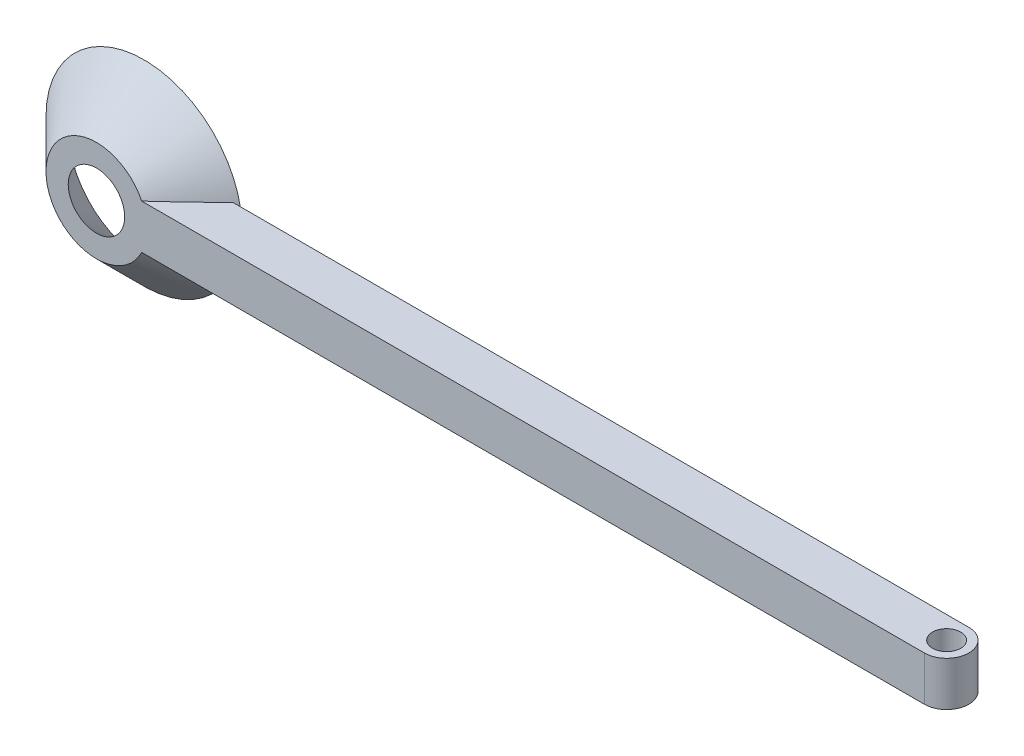
SolidWorks part; units mm, degrees
ref_plane "Front Plane" through (0, 0, 0) normal (0, 0, 1) x (1, 0, 0)
ref_plane "Top Plane" through (0, 0, 0) normal (0, 1, 0) x (1, 0, 0)
ref_plane "Right Plane" through (0, 0, 0) normal (1, 0, 0) x (0, 0, -1)
sketch "Sketch1" plane through (0, 0, 0) normal (0, 1, 0) x (1, 0, 0)
  line L1 (90, -5) -> (-90, -5)
  line L3 (90, 5) -> (-90, 5)
  line L4 (-90, -5) -> (-90, 5)
  line L5 (90, -5) -> (-90, 5) construction
  line L6 (90, 5) -> (-90, -5) construction
  line L7 (2.3241, -0.4022) -> (2.3241, -0.4064)
  arc A0 (90, 5) -> (90, -5) centre (90, 0) cw
  circle A1 centre (90, 0) radius 3.175
  point P0 (0, 0)
  dimension "D3" = 6.35
  dimension "D1" = 10
  dimension "D2" = 180
extrude "Boss-Extrude2" add sketch "Sketch1" along normal blind 5 and the other way blind 5 contours A0 L3 L4 L1 A1 region at (0.4245, 0, 0)
sketch "Sketch8" plane through (0, 0, 0) normal (0, 1, 0) x (1, 0, 0)
  line L0 (-96.35, 14.1668) -> (-96.35, -10.0145) construction
  line L1 (-90, -5) -> (-90, 5) construction
  line L2 (-85, -5) -> (-74.2702, 5.7298)
  line L3 (90, -5) -> (-90, -5) construction
  line L4 (-74.2702, 5.7298) -> (-79.2702, 5.7298)
  line L5 (-79.2702, 5.7298) -> (-90, -5)
  line L6 (-90, -5) -> (-85, -5)
  dimension "D1" = 6.35
  dimension "D2" = 5
  dimension "D3" = 19.05
  dimension "D4" = 6.35
  dimension "D6" = 45
revolve "Revolve3" add sketch "Sketch8" angle 360 about L0
sketch "Sketch10" plane through (0, 0, 0) normal (0, 1, 0) x (1, 0, 0)
  line L0 (-96.35, 5.7298) -> (-96.35, -5) construction
  line L1 (-79.2702, 5.7298) -> (-113.4298, 5.7298) construction
  line L2 (-102.7, -5) -> (-90, -5) construction
  line L3 (-96.35, 5.7298) -> (-79.2702, 5.7298)
  line L4 (-74.2702, 5.7298) -> (-118.4298, 5.7298) construction
  line L5 (-79.2702, 5.7298) -> (-90, -5)
  line L6 (-90, -5) -> (-96.35, -5)
  line L7 (-96.35, -5) -> (-96.35, 5.7298)
  line L8 (-80, 5) -> (-79.2702, 5.7298) construction
revolve "Cut-Revolve3" cut sketch "Sketch10" angle 360 about L0
